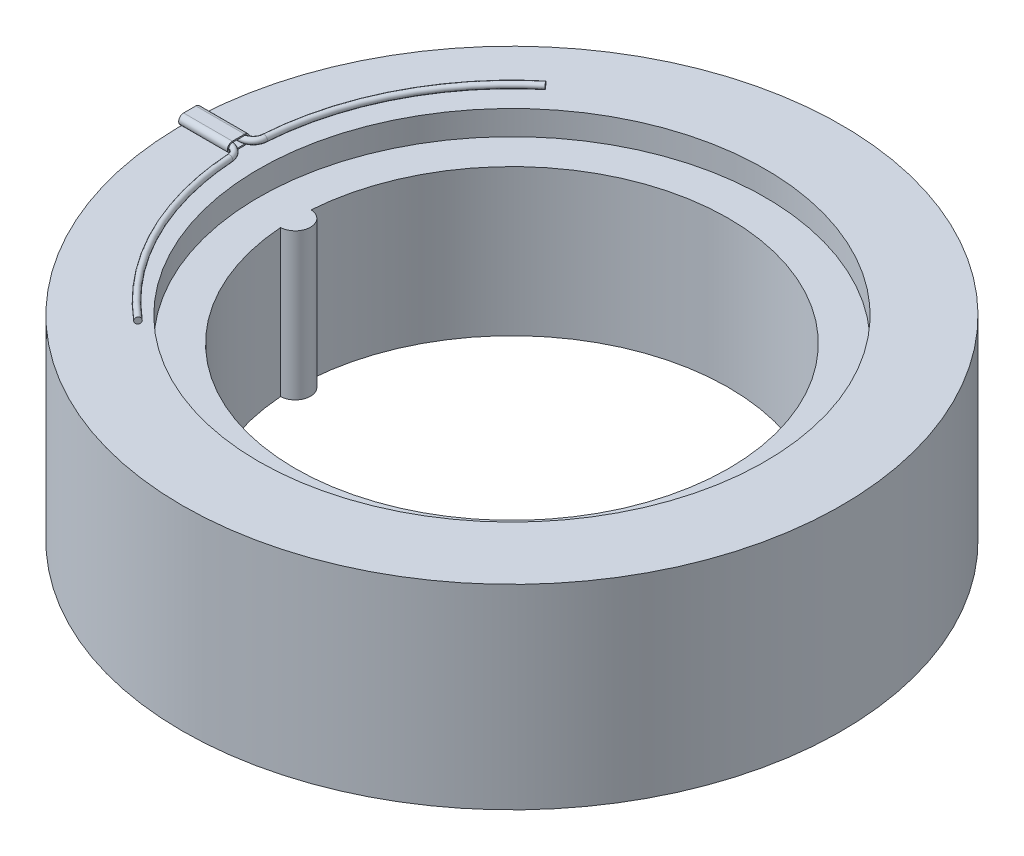
SolidWorks part; units mm, degrees
ref_plane "Front Plane" through (0, 0, 0) normal (0, 0, 1) x (1, 0, 0)
ref_plane "Top Plane" through (0, 0, 0) normal (0, 1, 0) x (1, 0, 0)
ref_plane "Right Plane" through (0, 0, 0) normal (1, 0, 0) x (0, 0, -1)
ref_axis "Axis1" through (0, 0, 0) along (0, 1, 0)
sketch "Sketch1" plane through (0, 0, 0) normal (0, 0, 1) x (1, 0, 0)
  line L0 (0, 0) -> (0, -11959.2771) construction
  line L1 (-17.75, 6) -> (-17.75, -6)
  line L2 (-17.75, 6) -> (-20.75, 6)
  line L3 (-20.75, 6) -> (-20.75, -6)
  line L4 (-20.75, -6) -> (-17.75, -6)
  point P5 (-17.75, 0)
  dimension "D1" = 35.5
  dimension "D2" = 12
  dimension "D3" = 3
revolve "Revolve1" add sketch "Sketch1" angle 360 about L0
sketch "Sketch2" plane through (0, 0, 0) normal (0, 0, 1) x (1, 0, 0)
  line L0 (-20.75, 6) -> (-20.75, -6) construction
  line L1 (-20.75, 8) -> (-27, 8)
  line L2 (-20.75, 8) -> (-20.75, -8)
  line L3 (-20.75, -8) -> (-27, -8)
  line L4 (-27, 8) -> (-27, -8)
  point P6 (-20.75, 0)
  dimension "D1" = 16
  dimension "D2" = 27
revolve "Revolve2" add sketch "Sketch2" angle 360 about L0
sketch "Sketch3" plane through (0, 0, 0) normal (0, 1, 0) x (1, 0, 0)
  circle A0 centre (-17.75, 0) radius 1.25
  circle A1 centre (0, 0) radius 17.75 construction
  dimension "D1" = 2.5
extrude "Boss-Extrude1" add sketch "Sketch3" along normal up to surface and the other way up to surface up to face at (0, 6, 20.75) other way up to face at (0, -6, 17.75)
ref_plane "Plane1" through (0, 9, 0) normal (0, 1, 0) x (1, 0, 0)
sketch "Sketch4" plane through (0, 9, 0) normal (0, 1, 0) x (1, 0, 0)
  line L0 (0, 0) -> (-50000, 0) construction
  line L1 (-25.8074, 0.5) -> (-22.7005, 0.5)
  arc A0 (-21.7027, 1.4341) -> (-13.9459, 16.6906) centre (0, 0) cw
  arc A1 (-22.7005, 0.5) -> (-21.7027, 1.4341) centre (-22.7005, 1.5) ccw
  circle A2 centre (0, 0) radius 20.75 construction
  dimension "D1" = 1
  dimension "D2" = 1
  dimension "D3" = 1
sweep "Sweep1" add path "Sketch4" circular profile diameter 0.5 parameters "D3"=0.5
mirror "Mirror2" about plane through (0, 0, 0) normal (0, 0, 1) of bodies 104
sketch "Sketch23" plane through (0, 0, 0) normal (1, 0, 0) x (0, 0, -1)
  line L0 (0.5, 9) -> (-0.5, 9) construction
  line L1 (0.5, 8.6967) -> (-0.5, 8.6967)
  line L2 (0.5, 9.3033) -> (-0.5, 9.3033)
  arc A0 (0.5, 8.6967) -> (0.5, 9.3033) centre (0.5, 9) ccw
  arc A1 (-0.5, 9.3033) -> (-0.5, 8.6967) centre (-0.5, 9) ccw
  point P4 (0, 9)
extrude "Extrude-Thin1" add sketch "Sketch23" against normal blind 4 from offset 22.4 separate body thin offset against normal yes thin type one direction wall 0.1
